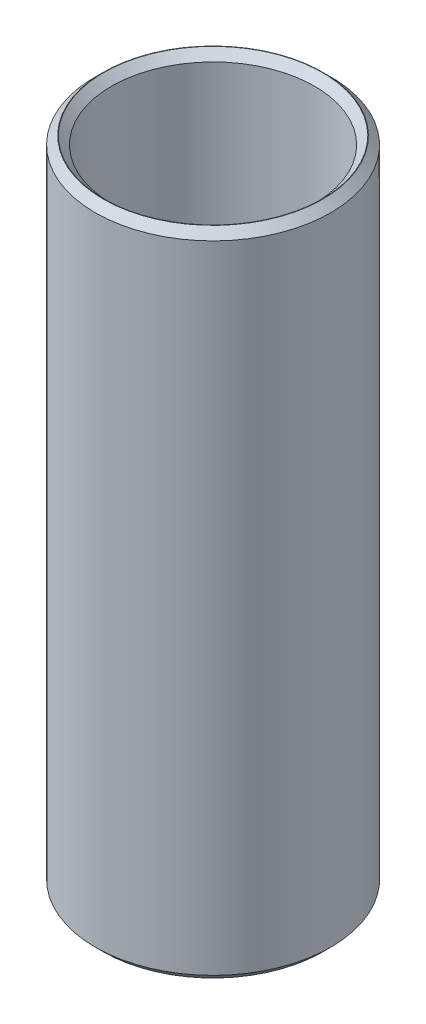
SolidWorks part; units mm, degrees
ref_plane "Front Plane" through (0, 0, 0) normal (0, 0, 1) x (1, 0, 0)
ref_plane "Top Plane" through (0, 0, 0) normal (0, 1, 0) x (1, 0, 0)
ref_plane "Right Plane" through (0, 0, 0) normal (1, 0, 0) x (0, 0, -1)
sketch "Sketch1" plane through (0, 0, 0) normal (0, 1, 0) x (1, 0, 0)
  circle A0 centre (0, 0) radius 37.5
  dimension "SLEEVE_OD" = 75
extrude "Boss-Extrude1" add sketch "Sketch1" along normal blind 207.6063
sketch "Sketch2" plane through (0, 0, 0) normal (0, 1, 0) x (1, 0, 0)
  circle A0 centre (0, 0) radius 32.3397
  dimension "BORE_D" = 64.6793
extrude "Cut-Extrude1" cut sketch "Sketch2" along normal through all
chamfer "Chamfer1" distance 2.5133 angle 45 4 edges at (0, 207.6063, 32.3397) (0, 0, 32.3397) (0, 0, 37.5) (0, 207.6063, 37.5)
